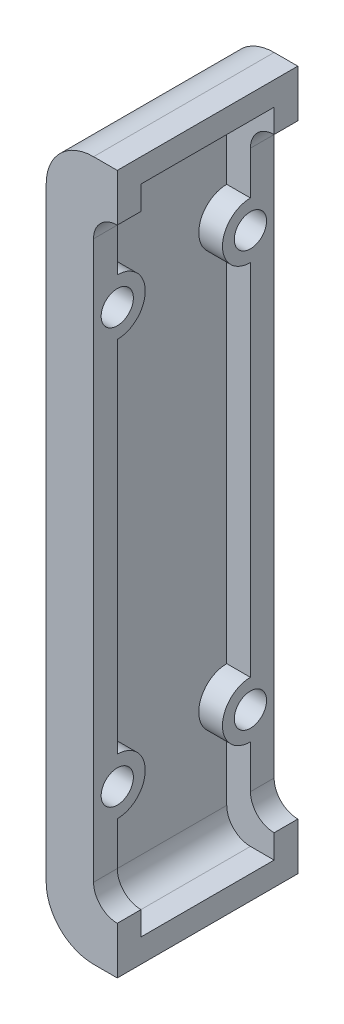
SolidWorks part; units mm, degrees
material "1060 Alloy"
ref_plane "Front Plane" through (0, 0, 0) normal (0, 0, 1) x (1, 0, 0)
ref_plane "Top Plane" through (0, 0, 0) normal (0, 1, 0) x (1, 0, 0)
ref_plane "Right Plane" through (0, 0, 0) normal (1, 0, 0) x (0, 0, -1)
sketch "Sketch1" plane through (0, 0, 0) normal (0, 0, 1) x (1, 0, 0)
  line L0 (0, 63.8) -> (0, -63.8)
  line L1 (0, 63.8) -> (5, 63.8)
  line L2 (5, 63.8) -> (5, 73.8)
  line L3 (5, 73.8) -> (-10, 73.8)
  line L4 (-10, 73.8) -> (-10, -73.8)
  line L5 (-10, -73.8) -> (5, -73.8)
  line L6 (5, -73.8) -> (5, -63.8)
  line L7 (5, -63.8) -> (0, -63.8)
  dimension "D1" = 127.6
  dimension "D2" = 5
  dimension "D3" = 10
  dimension "D4" = 10
extrude "Boss-Extrude1" add sketch "Sketch1" along normal mid plane 38.1
sketch "Sketch3" plane through (0, 0, 0) normal (1, 0, 0) x (0, 0, -1)
  line L0 (19.05, -63.8) -> (19.05, 63.8) construction
  line L1 (-14.05, -68.8) -> (14.05, -68.8)
  line L2 (-14.05, -68.8) -> (-14.05, 68.8)
  line L3 (-14.05, 68.8) -> (14.05, 68.8)
  line L4 (14.05, -68.8) -> (14.05, 68.8)
  line L5 (-14.05, -68.8) -> (14.05, 68.8) construction
  line L6 (-14.05, 68.8) -> (14.05, -68.8) construction
  line L7 (-19.05, 73.8) -> (19.05, 73.8) construction
  point P0 (0, 0)
  dimension "D1" = 5
  dimension "D2" = 5
extrude "Cut-Extrude1" cut sketch "Sketch3" along normal through all and the other way blind 5
fillet "Fillet1" radius 5 6 edges at (0, -63.8, 16.55) (0, -63.8, -16.55) (0, 63.8, 16.55) (0, 63.8, -16.55) (-5, -68.8, 0) (-5, 68.8, 0)
fillet "Fillet2" radius 10 2 edges at (-10, -73.8, 0) (-10, 73.8, 0)
hole_wizard "Tap Drill for M8x1.25 Tap1" positions "Sketch5" profile "Sketch4" hole size "M8x1.25" standard "ANSI Metric"
sketch "Sketch5" plane through (-10, 0, 0) normal (-1, 0, 0) x (0, 0, 1)
  line L0 (-19.05, 63.8) -> (-19.05, -63.8) construction
  line L2 (19.05, 63.8) -> (19.05, -63.8) construction
  line L4 (-19.05, 58.8) -> (-14.05, 58.8) construction
  line L5 (14.05, 58.8) -> (19.05, 58.8) construction
  line L6 (-14.05, -58.8) -> (-19.05, -58.8) construction
  line L7 (19.05, -58.8) -> (14.05, -58.8) construction
  point P0 (-14.05, 43.8)
  point P2 (14.05, 43.8)
  point P4 (-14.05, -43.8)
  point P6 (14.05, -43.8)
  point P21 (-16.55, -58.8)
  dimension "D1" = 5
  dimension "D2" = 15
  dimension "D3" = 5
  dimension "D4" = 15
  dimension "D5" = 15
  dimension "D6" = 5
  dimension "D7" = 5
  dimension "D8" = 15
sketch "Sketch4" plane through (-10, 43.8, -14.05) normal (0, 1, 0) x (0, 0, 1)
  line L0 (0, 0) -> (0, 14.0429)
  line L1 (0, 14.0429) -> (3.4, 12)
  line L2 (3.4, 12) -> (3.4, 0)
  line L5 (3.4, 0) -> (0, 0)
  line L10 (0, 14.0429) -> (-3.4, 12) construction
  line L11 (0, -6.35) -> (0, 107.95) construction
  dimension "Hole Dia." = 6.8
  dimension "Hole Depth" = 12
  dimension "Drill Angle" = 118
cosmetic thread "Cosmetic Thread1" parameters "D2"=8
cosmetic thread "Cosmetic Thread2" parameters "D2"=8
cosmetic thread "Cosmetic Thread3" parameters "D2"=8
cosmetic thread "Cosmetic Thread4" parameters "D2"=8
sketch "Sketch6" plane through (-5, 0, 0) normal (1, 0, 0) x (0, 0, -1)
  line L0 (-14.05, 63.8) -> (-14.05, 47.2) construction
  line L1 (-14.05, -40.4) -> (-14.05, 40.4) construction
  line L2 (-14.05, 49.7) -> (-14.05, 47.2)
  line L3 (-14.05, 40.4) -> (-14.05, 37.9)
  line L4 (14.05, 58.8) -> (14.05, 47.2) construction
  line L5 (14.05, -40.4) -> (14.05, 40.4) construction
  line L6 (14.05, 49.7) -> (14.05, 47.2)
  line L7 (14.05, 47.2) -> (14.112, 47.1771)
  line L8 (14.05, 40.4) -> (14.05, 37.9)
  line L9 (-14.05, 40.4) -> (-14.05, -40.4) construction
  line L10 (-14.05, -37.9) -> (-14.05, -40.4)
  line L11 (-14.05, -47.2) -> (-14.05, -49.7)
  line L12 (-14.05, -37.9) -> (-14.05, -40.4)
  line L13 (-14.05, -49.7) -> (-14.05, -47.2)
  line L14 (14.05, 40.4) -> (14.05, -40.4) construction
  line L15 (14.05, -47.2) -> (14.05, -58.8) construction
  line L16 (14.05, -37.9) -> (14.05, -40.4)
  line L18 (14.05, -47.2) -> (14.05, -49.7)
  arc A0 (-14.05, 47.2) -> (-14.05, 40.4) centre (-14.05, 43.8) cw
  arc A1 (-14.05, 49.7) -> (-14.05, 37.9) centre (-14.05, 43.8) cw
  arc A2 (14.05, 47.2) -> (14.05, 40.4) centre (14.05, 43.8) ccw
  arc A3 (14.05, 49.7) -> (14.05, 37.9) centre (14.05, 43.8) ccw
  arc A4 (-14.05, -40.4) -> (-14.05, -47.2) centre (-14.05, -43.8) cw
  arc A7 (-14.05, -37.9) -> (-14.05, -49.7) centre (-14.05, -43.8) cw
  arc A8 (14.05, -40.4) -> (14.05, -47.2) centre (14.05, -43.8) ccw
  arc A9 (14.05, -37.9) -> (14.05, -49.7) centre (14.05, -43.8) ccw
  line M1 (14.05, -40.4) -> (14.05, 40.4)
  arc M2 (14.05, 40.4) -> (14.05, 47.2) centre (14.05, 43.8) cw
  line M3 (14.05, 47.2) -> (14.05, 63.8)
  line M7 (-14.05, 40.4) -> (-14.05, -40.4)
  arc M8 (-14.05, -40.4) -> (-14.05, -47.2) centre (-14.05, -43.8) cw
  line M9 (-14.05, -47.2) -> (-14.05, -63.8)
  line M11 (14.05, -63.8) -> (14.05, -47.2)
  arc M12 (14.05, -47.2) -> (14.05, -40.4) centre (14.05, -43.8) cw
  dimension "D1" = 3.4
  dimension "D2" = 2.5
  dimension "D3" = 3.4
  dimension "D4" = 2.5
  dimension "D5" = 3.4
  dimension "D6" = 2.5
  dimension "D7" = 3.4
  dimension "D8" = 2.5
extrude "Boss-Extrude2" add sketch "Sketch6" along normal up to surface (5 mm away) contours A9 M1 M11 M12 | A7 M7 M8 M9 | A3 M3 M1 M2 | A1 L3 A0 L2 up to face at (0, 0, 16.15)
